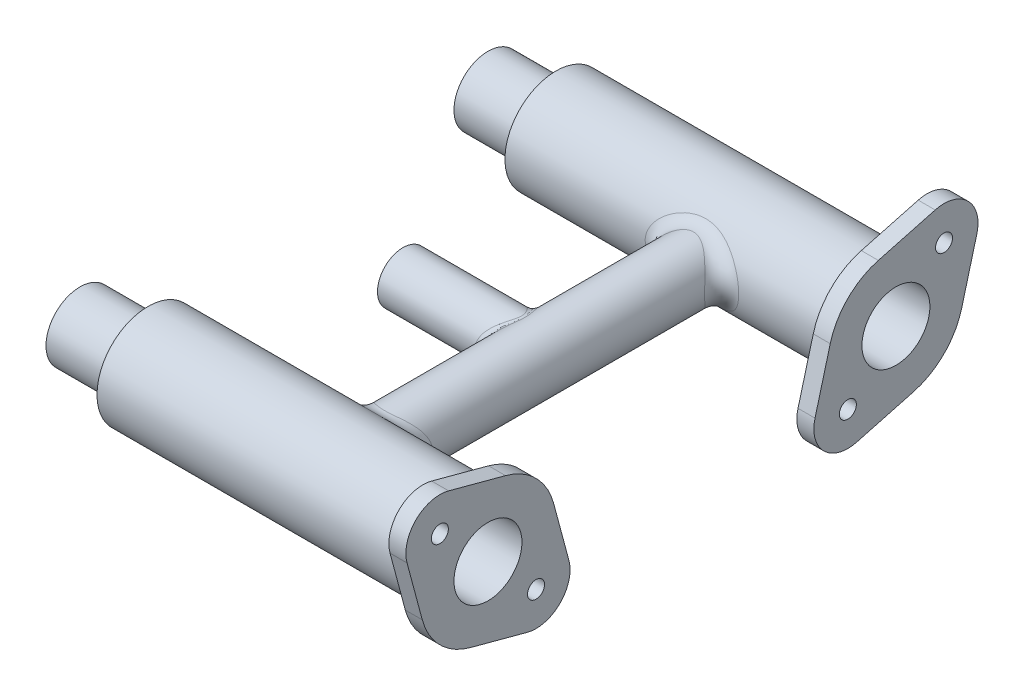
SolidWorks part; units mm, degrees
note: '?' marks a value the reader was unsure of.
ref_plane "Front" through (0, 0, 0) normal (0, 0, 1) x (1, 0, 0)
ref_plane "Top" through (0, 0, 0) normal (0, 1, 0) x (1, 0, 0)
ref_plane "Right" through (0, 0, 0) normal (1, 0, 0) x (0, 0, -1)
sketch "Sketch3" plane through (0, 0, 0) normal (0, 0, 1) x (1, 0, 0)
  circle A0 centre (0, 0) radius 5.5562
  dimension "D1" = 11.1125
extrude "Base-Extrude" add sketch "Sketch3" along normal mid plane 76.2
sketch "Sketch6" plane through (0, 0, 0) normal (1, 0, 0) x (0, -1, 0)
  circle A0 centre (0, 0) radius 4.7625
  dimension "D1" = 9.525
extrude "Boss-Extrude1" add sketch "Sketch6" against normal blind 25.4
fillet "Fillet2" radius 1.5875 1 edges at (-5.5154, 0.6726, -4.7148)
sketch "Sketch4" plane through (0, 0, 38.1) normal (0, 0, 1) x (1, 0, 0)
  line L0 (-47.625, 0) -> (66.675, 0) construction
  line L1 (-47.625, 0) -> (-47.625, -6.35)
  line L2 (-47.625, -6.35) -> (-34.925, -6.35)
  line L3 (-34.925, -6.35) -> (-34.925, -9.525)
  line L4 (-34.925, -9.525) -> (28.575, -9.525)
  line L5 (28.575, 0) -> (28.575, -9.525)
  line L6 (-47.625, 0) -> (28.575, 0)
  circle A0 centre (0, 0) radius 5.5562 construction
  dimension "D1" = 47.625
  dimension "D2" = 76.2
  dimension "D3" = 6.35
  dimension "D4" = 9.525
  dimension "D5" = 12.7
revolve "Boss-Revolve2" add sketch "Sketch4" angle 360 about L0
fillet "Fillet1" radius 3.175 1 edges at (5.3272, -1.5789, 28.7068)
sketch "Sketch5" plane through (28.575, 0, 0) normal (1, 0, 0) x (0, 0, -1)
  circle A0 centre (-38.1, 0) radius 6.35
  dimension "D1" = 12.7
sketch "Sketch7" plane through (28.575, 0, 0) normal (1, 0, 0) x (0, 0, -1)
  line L0 (-38.1, 0) -> (-12.7616, 0) construction
  line L1 (-62.4743, 24.3743) -> (-18.4816, -19.6184) construction
  line L2 (-45.4368, 15.1139) -> (-34.813, 12.2673)
  line L3 (-53.2139, 7.3368) -> (-50.3673, -3.287)
  line L4 (-38.1, 0) -> (-60.2521, -22.1521) construction
  line L5 (-30.7632, -15.1139) -> (-41.387, -12.2673)
  line L6 (-22.9861, -7.3368) -> (-25.8327, 3.287)
  arc A0 (-53.2139, 7.3368) -> (-45.4368, 15.1139) centre (-47.0803, 8.9803) cw
  arc A1 (-30.7632, -15.1139) -> (-22.9861, -7.3368) centre (-29.1197, -8.9803) ccw
  arc A2 (-25.8327, 3.287) -> (-34.813, 12.2673) centre (-38.1, 0) ccw
  arc A3 (-50.3673, -3.287) -> (-41.387, -12.2673) centre (-38.1, 0) ccw
  circle A4 centre (-47.0803, 8.9803) radius 1.5875
  circle A5 centre (-29.1197, -8.9803) radius 1.5875
  dimension "D2" = 12.7
  dimension "D3" = 6.35
  dimension "D5" = 3.175
  dimension "D1" = 45
  dimension "D4" = 12.7
extrude "Boss-Extrude2" add sketch "Sketch7" against normal blind 3.175
extrude "Cut-Extrude1" cut sketch "Sketch5" against normal blind 25.4
mirror "Mirror1" about plane through (0, 0, 0) normal (0, 0, 1) of "Cut-Extrude1", "Boss-Extrude2", "Fillet1", "Boss-Revolve2"
ref_axis "Axis1" through (-75.4, 0, 0) along (1, 0, 0)?
sketch "Sketch8" plane through (-25.4, 0, 0) normal (-1, 0, 0) x (0, -1, 0)
  point P0 (0, 0)
